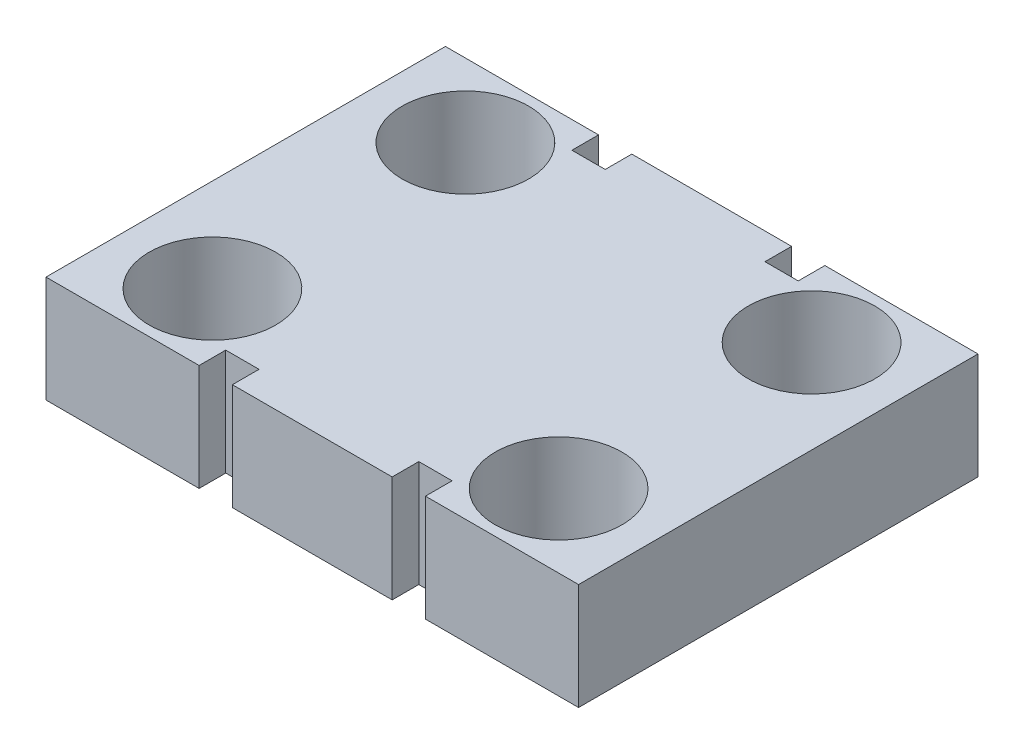
SolidWorks part; units mm, degrees
ref_plane "Płaszczyzna przednia" through (0, 0, 0) normal (0, 0, 1) x (1, 0, 0)
ref_plane "Płaszczyzna górna" through (0, 0, 0) normal (0, 1, 0) x (1, 0, 0)
ref_plane "Płaszczyzna prawa" through (0, 0, 0) normal (1, 0, 0) x (0, 0, -1)
sketch "Sketch1" plane through (0, 0, 0) normal (0, 1, 0) x (1, 0, 0)
  line L1 (-40, 30) -> (0, 30)
  line L2 (-40, 30) -> (-40, 0)
  line L3 (-40, 0) -> (0, 0)
  line L4 (0, 30) -> (0, 0)
  dimension "D1" = 40
  dimension "D2" = 30
extrude "Boss-Extrude1" add sketch "Sketch1" along normal blind 8
sketch "Sketch2" plane through (0, 8, 0) normal (0, 1, 0) x (1, 0, 0)
  line L0 (-40, 15) -> (-9.7076, 15) construction
  line L1 (-20, 30) -> (-20, -8.7627) construction
  line L2 (-40, 30) -> (-40, 0) construction
  line L3 (0, 30) -> (-40, 30) construction
  circle A0 centre (-33, 24.5) radius 4.75
  circle A1 centre (-33, 5.5) radius 4.75
  circle A2 centre (-7, 5.5) radius 4.75
  circle A3 centre (-7, 24.5) radius 4.75
  dimension "D1" = 9.5
  dimension "D2" = 7
  dimension "D3" = 5.5
extrude "Cut-Extrude1" cut sketch "Sketch2" against normal blind 7
sketch "Sketch3" plane through (0, 0, 0) normal (0, -1, 0) x (1, 0, 0)
  line L0 (-40, 0) -> (0, -30) construction
  circle A0 centre (-20, -15) radius 5.5
  point P3 (-20, -15)
  dimension "D1" = 11
extrude "Cut-Extrude2" cut sketch "Sketch3" against normal blind 6
sketch "Sketch4" plane through (0, 0, 0) normal (0, -1, 0) x (1, 0, 0)
  line L0 (-20, 0) -> (-20, -30) construction
  line L1 (-40, -15) -> (0, -15) construction
  line L2 (-40, 0) -> (0, 0) construction
  line L3 (0, -30) -> (-40, -30) construction
  line L4 (-40, -30) -> (-40, 0) construction
  line L5 (0, 0) -> (0, -30) construction
  line L6 (-11.5, -2) -> (-14, -2)
  line L7 (-28.5, 0) -> (-26, 0)
  line L8 (-28.5, 0) -> (-28.5, -2)
  line L9 (-28.5, -2) -> (-26, -2)
  line L10 (-26, 0) -> (-26, -2)
  line L11 (-14, 0) -> (-14, -2)
  line L12 (-11.5, 0) -> (-14, 0)
  line L13 (-11.5, 0) -> (-11.5, -2)
  line L14 (-11.5, -30) -> (-11.5, -28)
  line L15 (-11.5, -30) -> (-14, -30)
  line L16 (-14, -30) -> (-14, -28)
  line L17 (-11.5, -28) -> (-14, -28)
  line L18 (-28.5, -28) -> (-26, -28)
  line L19 (-26, -30) -> (-26, -28)
  line L20 (-28.5, -30) -> (-26, -30)
  line L21 (-28.5, -30) -> (-28.5, -28)
  dimension "D1" = 2.5
  dimension "D2" = 2
  dimension "D3" = 6
extrude "Cut-Extrude3" cut sketch "Sketch4" against normal blind 15
